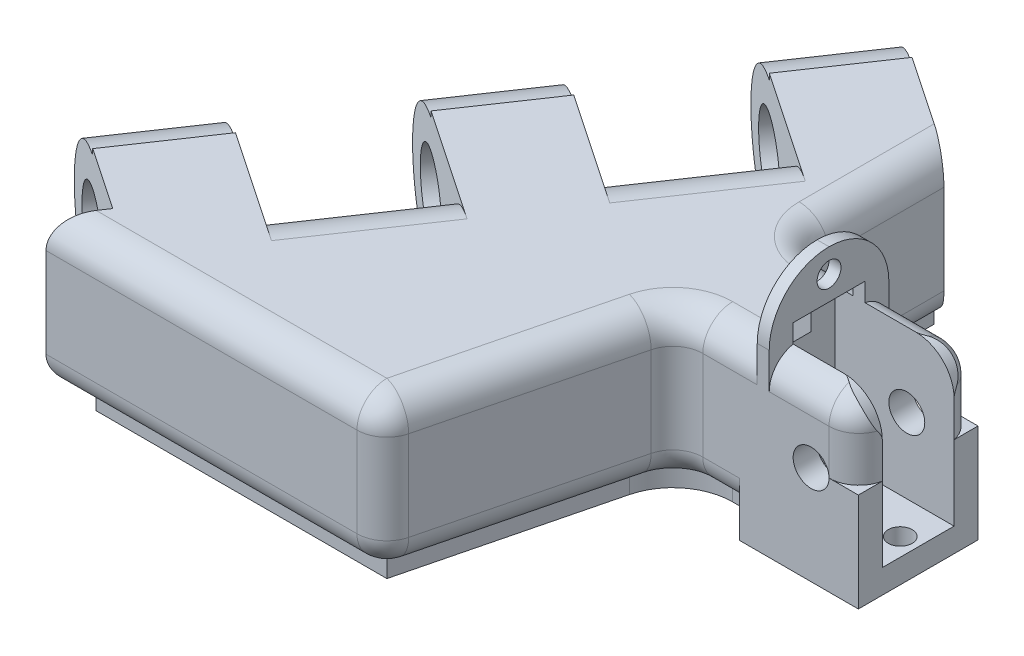
SolidWorks part; units mm, degrees
ref_plane "Front" through (0, 0, 0) normal (0, 0, 1) x (1, 0, 0)
ref_plane "Top" through (0, 0, 0) normal (0, 1, 0) x (1, 0, 0)
ref_plane "Right" through (0, 0, 0) normal (1, 0, 0) x (0, 0, -1)
sketch "Sketch1" plane through (0, 0, 0) normal (0, 1, 0) x (1, 0, 0)
  line L0 (-60, 60) -> (-60, 80)
  line L1 (-60, -60) -> (60, -60)
  line L2 (-60, -60) -> (-60, 60)
  line L3 (-60, 60) -> (60, 60)
  line L4 (60, -60) -> (60, 60)
  line L5 (-60, -60) -> (60, 60) construction
  line L6 (-60, 60) -> (60, -60) construction
  line L7 (-60, 80) -> (-40, 80)
  line L8 (-40, 80) -> (-40, 60)
  line L9 (-26.6667, 60) -> (-26.6667, 90)
  line L10 (-26.6667, 90) -> (-6.6667, 90)
  line L11 (-6.6667, 90) -> (-6.6667, 60)
  line L12 (-6.6667, 60) -> (6.6667, 60)
  line L13 (6.6667, 60) -> (6.6667, 90)
  line L14 (6.6667, 90) -> (26.6667, 90)
  line L15 (26.6667, 90) -> (26.6667, 60)
  line L16 (40, 60) -> (40, 80)
  line L17 (40, 80) -> (60, 80)
  line L18 (60, 80) -> (60, 60)
  line L19 (60, 0) -> (90, 0)
  line L20 (90, 0) -> (90, -20)
  line L21 (90, -20) -> (60, -20)
  point P0 (0, 0)
  dimension "D1" = 120
  dimension "D2" = 90
  dimension "D3" = 20
  dimension "D4" = 20
  dimension "D5" = 20
  dimension "D6" = 20
  dimension "D7" = 13.3333
  dimension "D8" = 13.3333
  dimension "D9" = 120
  dimension "D10" = 20
  dimension "D11" = 30
  dimension "D12" = 30
  dimension "D13" = 20
  dimension "D14" = 90
  dimension "D15" = 30
  dimension "D16" = 40
  dimension "D17" = 20
extrude "Boss-Extrude1" add sketch "Sketch1" along normal blind 25 contours L1 L4 L3 L2 | L18 L17 L16 L3 | L14 L13 L3 | L11 L10 L9 L3 | L8 L7 L0 L3 | L20 L19 L4 region at (0, 0, 0) region at (-50, 0, -70) region at (-16.6667, 0, -75) region at (75, 0, 10) region at (16.6667, 0, -75) region at (50, 0, -70)
sketch "Sketch3" plane through (0, 25, 0) normal (0, 1, 0) x (1, 0, 0)
  line L0 (-60, 5) -> (-30, -60)
  line L1 (-60, -60) -> (-60, 80) construction
  line L2 (-60, -60) -> (60, -60) construction
  line L3 (-30, -60) -> (-60, -60)
  line L4 (-60, -60) -> (-60, 5)
  line L5 (50, -60) -> (60, -20)
  line L6 (-60, -60) -> (60, -60) construction
  line L7 (60, -60) -> (60, -20) construction
  line L8 (60, -20) -> (60, -60)
  line L9 (60, -60) -> (50, -60)
  dimension "D1" = 40
  dimension "D2" = 10
  dimension "D3" = 30
  dimension "D4" = 65
extrude "Cut-Extrude2" cut sketch "Sketch3" against normal blind 50
sketch "Sketch5" plane through (0, 25, 0) normal (0, 1, 0) x (1, 0, 0)
fillet "Fillet3" radius 5 51 edges at (0, 25, -60) (0, 0, -60) (33.3333, 25, -60) (-33.3333, 25, -60) (-33.3333, 0, -60) (33.3333, 0, -60) (75, 25, 0) (75, 0, 0) (75, 0, 20) (75, 25, 20) (-40, 12.5, -60) (-40, 25, -70) (-40, 12.5, -80) (-40, 0, -70) (-26.6667, 12.5, -90) (-26.6667, 25, -75) (-26.6667, 12.5, -60) (-26.6667, 0, -75) (-6.6667, 12.5, -60) (-6.6667, 25, -75) (-6.6667, 12.5, -90) (-6.6667, 0, -75) (6.6667, 12.5, -90) (6.6667, 25, -75) (6.6667, 12.5, -60) (6.6667, 0, -75) (26.6667, 12.5, -60) (26.6667, 25, -75) (26.6667, 12.5, -90) (26.6667, 0, -75) (40, 12.5, -80) (40, 25, -70) (40, 12.5, -60) (40, 0, -70) (60, 12.5, 0) (60, 25, -40) (60, 12.5, -80) (60, 0, -40) (55, 0, 40) (55, 25, 40) (60, 12.5, 20) (50, 12.5, 60) (10, 0, 60) (10, 25, 60) (-45, 0, 27.5) (-45, 25, 27.5) (-30, 12.5, 60) (-60, 0, -42.5) (-60, 12.5, -80) (-60, 25, -42.5) (-60, 12.5, -5)
fillet "Fillet4" radius 5 32 edges at (41.4645, 1.4645, -78.5355) (58.5355, 1.4645, -78.5355) (8.1311, 1.4645, -88.5355) (25.2022, 1.4645, -88.5355) (-25.2022, 1.4645, -88.5355) (-8.1311, 1.4645, -88.5355) (-58.5355, 1.4645, -78.5355) (-41.4645, 1.4645, -78.5355) (-25.2022, 23.5355, -88.5355) (-8.1311, 23.5355, -88.5355) (8.1311, 23.5355, -88.5355) (25.2022, 23.5355, -88.5355) (41.4645, 23.5355, -78.5355) (58.5355, 23.5355, -78.5355) (90, 23.5355, 1.4645) (90, 12.5, 0) (90, 1.4645, 1.4645) (90, 1.4645, 18.5355) (90, 12.5, 20) (90, 23.5355, 18.5355) (-58.5355, 23.5355, -78.5355) (-41.4645, 23.5355, -78.5355) (90, 0, 10) (50, 0, -80) (16.6667, 0, -90) (-16.6667, 0, -90) (-50, 0, -80) (-16.6667, 25, -90) (16.6667, 25, -90) (50, 25, -80) (90, 25, 10) (-50, 25, -80)
sketch "Sketch6" plane through (0, 25, 0) normal (0, 1, 0) x (1, 0, 0)
  line L0 (-2.5008, -55) -> (55, 30) construction
  line L1 (-26.8008, -55) -> (46.0961, -55) construction
  line L2 (55, 5) -> (55, 75) construction
  line L3 (55, 5) -> (55, 55) construction
  line L5 (126.972, 136.3919) -> (-26.8008, -90.9212)
  line L9 (-26.8008, -90.9212) -> (-300.5369, -90.9212)
  line L10 (-300.5369, -90.9212) -> (-300.5369, 228.057)
  line L11 (-300.5369, 228.057) -> (126.972, 228.057)
  line L12 (126.972, 228.057) -> (126.972, 136.3919)
  point P10 (55, 30)
  dimension "D1" = 24.3
  dimension "D2" = 427.5089
  dimension "D3" = 318.9783
  dimension "D4" = 90
  dimension "D5" = 273.736
extrude "Cut-Extrude4" cut sketch "Sketch6" against normal through all
sketch "Sketch7" plane through (23.8097, 0, 16.1068) normal (-0.8283, 0, -0.5603) x (-0.5603, 0, 0.8283)
  line L0 (46.9566, 25) -> (-55.6657, 25) construction
  line L1 (44.9566, 0) -> (27.7766, 0)
  line L2 (44.9566, 0) -> (44.9566, 25)
  line L3 (44.9566, 25) -> (27.7766, 25)
  line L4 (27.7766, 0) -> (27.7766, 25)
  line L5 (46.9566, 0) -> (-55.6657, 0) construction
  line L6 (4.2355, 0) -> (-12.9445, 0)
  line L7 (4.2355, 0) -> (4.2355, 25)
  line L8 (4.2355, 25) -> (-12.9445, 25)
  line L9 (-12.9445, 0) -> (-12.9445, 25)
  line L10 (27.7766, 0) -> (-36.4857, 0) construction
  line L11 (-53.6657, 0) -> (-36.4857, 0)
  line L12 (-53.6657, 0) -> (-53.6657, 25)
  line L13 (-53.6657, 25) -> (-36.4857, 25)
  line L14 (-36.4857, 0) -> (-36.4857, 25)
  point P18 (-4.3545, 0)
  dimension "D1" = 17.18
  dimension "D2" = 2
  dimension "D3" = 17.18
  dimension "D4" = 17.18
  dimension "D5" = 2
extrude "Boss-Extrude2" add sketch "Sketch7" along normal blind 25
fillet "Fillet5" radius 10 4 edges at (37.6579, 0, -4.3643) (37.6579, 25, -4.3643) (14.8412, 0, 29.3643) (14.8412, 25, 29.3643)
sketch "Sketch8" plane through (-25.1899, 0, 37.2367) normal (-0.5603, 0, 0.8283) x (0.8283, 0, 0.5603)
  line L0 (3.7459, 0) -> (28.7459, 0) construction
  line L1 (3.7459, 25) -> (28.7459, 25) construction
  line L2 (16.2459, 0) -> (3.7459, 0)
  line L3 (3.7459, 0) -> (3.7459, 25)
  line L4 (3.7459, 25) -> (16.2459, 25)
  arc A0 (16.2459, 0) -> (16.2459, 25) centre (16.2459, 12.5) cw
  line M2 (28.7459, 25) -> (3.7459, 25)
  line M3 (3.7459, 25) -> (3.7459, 0)
  line M4 (3.7459, 0) -> (28.7459, 0)
extrude "Cut-Extrude5" cut sketch "Sketch8" against normal through all contours A0 L3 M4 | A0 M3 M2 region at (-19.7746, 22.2079, 40.9) region at (-19.7746, 2.7921, 40.9)
sketch "Sketch9" plane through (-25.1899, 0, 37.2367) normal (-0.5603, 0, 0.8283) x (0.8283, 0, 0.5603)
  circle A0 centre (16.2459, 12.5) radius 6.665
  arc A2 (16.2459, 25) -> (16.2459, 0) centre (16.2459, 12.5) ccw construction
  point P5 (3.7459, 12.5)
  dimension "D1" = 13.33
extrude "Cut-Extrude6" cut sketch "Sketch9" against normal through all
sketch "Sketch10" plane through (-25.1899, 0, 37.2367) normal (-0.5603, 0, 0.8283) x (0.8283, 0, 0.5603)
  line L0 (16.2459, 25) -> (16.2459, 24)
  line L1 (16.2459, 25) -> (-13.7541, 25)
  line L2 (-13.7541, 25) -> (-13.7541, 0)
  line L3 (-13.7541, 0) -> (16.2459, 0)
  line L4 (16.2459, 0) -> (16.2459, 1)
  arc A0 (16.2459, 1) -> (16.2459, 24) centre (16.2459, 12.5) cw
  dimension "D1" = 90
  dimension "D2" = 90
  dimension "D3" = 90
  dimension "D4" = 30
  dimension "D5" = 1
extrude "Cut-Extrude7" cut sketch "Sketch10" against normal through all
sketch "Sketch11" plane through (23.8097, 0, 16.1068) normal (-0.8283, 0, -0.5603) x (-0.5603, 0, 0.8283)
  line L1 (-53.6657, 0) -> (-73.6657, 0)
  line L2 (-53.6657, 0) -> (-53.6657, 25)
  line L3 (-53.6657, 25) -> (-73.6657, 25)
  line L4 (-73.6657, 0) -> (-73.6657, 25)
  dimension "D1" = 20
extrude "Cut-Extrude8" cut sketch "Sketch11" against normal blind 15
sketch "Sketch12" plane through (0, 25, 0) normal (0, 1, 0) x (1, 0, 0)
  line L1 (70, -4) -> (110, -4)
  line L2 (70, -4) -> (70, -16)
  line L3 (70, -16) -> (110, -16)
  line L4 (110, -4) -> (110, -16)
  line L5 (90, -5) -> (90, -15) construction
  line L6 (63.9039, -15) -> (85, -15) construction
  dimension "D1" = 20
  dimension "D2" = 12
  dimension "D3" = 40
  dimension "D4" = 1
extrude "Cut-Extrude9" cut sketch "Sketch12" against normal through all
sketch "Sketch13" plane through (0, 0, 20) normal (0, 0, 1) x (1, 0, 0)
  line L0 (85, 5) -> (85, 20) construction
  line L1 (82, 20) -> (82, 5) construction
  line L2 (85, 20) -> (63.9039, 20) construction
  line L3 (63.9039, 5) -> (85, 5) construction
  circle A0 centre (82, 12.5) radius 3
  dimension "D1" = 6
extrude "Cut-Extrude10" cut sketch "Sketch13" against normal through all
sketch "Sketch14" plane through (0, 0, 4) normal (0, 0, 1) x (1, 0, 0)
  line L0 (85, 24.899) -> (70, 24.899) construction
  line L1 (70, 0.101) -> (85, 0.101) construction
  line L2 (89.899, 5) -> (89.899, 20) construction
  line L3 (77.5, 24.899) -> (89.899, 24.899)
  line L4 (89.899, 24.899) -> (89.899, 0.101)
  line L5 (89.899, 0.101) -> (77.5, 0.101)
  arc A0 (77.5, 24.899) -> (77.5, 0.101) centre (77.5, 12.5) cw
  line M6 (70, 0.101) -> (85, 0.101)
  arc M7 (85, 0.101) -> (89.899, 5) centre (85, 5) ccw
  line M8 (89.899, 5) -> (89.899, 20)
  arc M9 (89.899, 20) -> (85, 24.899) centre (85, 20) ccw
  line M10 (85, 24.899) -> (70, 24.899)
extrude "Cut-Extrude11" [suppressed] cut sketch "Sketch14" against normal through all both and the other way through all contours L4 L3 M9 | A0 L4 M10 M9 | A0 M8 M6 M7 | L5 L4 M7
sketch "Sketch16" plane through (0, 0, 20) normal (0, 0, 1) x (1, 0, 0)
  line L0 (85, 12.5) -> (89.899, 12.5)
  line L1 (89.899, 20) -> (89.899, 5) construction
  line L2 (70, 12.5) -> (70, 0.101)
  line L3 (79, 12.5) -> (70, 12.5)
  line L4 (85, 0.101) -> (70, 0.101) construction
  line L5 (70, 0.101) -> (85, 0.101)
  line L6 (89.899, 12.5) -> (89.899, 5)
  line L7 (70, 0.101) -> (70, 24.899) construction
  circle A0 centre (82, 12.5) radius 3 construction
  arc A1 (85, 0.101) -> (89.899, 5) centre (85, 5) ccw
  arc A2 (79, 12.5) -> (85, 12.5) centre (82, 12.5) ccw
  dimension "D1" = 3
extrude "Boss-Extrude3" add sketch "Sketch16" against normal up to surface (20 mm away) up to face at (77.3333, 12.5, 0)
sketch "Sketch17" plane through (0, 12.5, 0) normal (0, 1, 0) x (1, 0, 0)
  line L1 (89.899, -16) -> (70, -16)
  line L2 (89.899, -16) -> (89.899, -4)
  line L3 (89.899, -4) -> (70, -4)
  line L4 (70, -16) -> (70, -4)
extrude "Cut-Extrude12" cut sketch "Sketch17" against normal through all
sketch "Sketch18" plane through (0, 0, 0) normal (0, -1, 0) x (-1, 0, 0)
  line L4 (-89.899, 0) -> (-89.899, -20)
  line L7 (-89.899, 0) -> (-89.899, -4) construction
  line L8 (-89.899, 0) -> (-70, 0)
  line L9 (-70, 0) -> (-70, -5)
  line L10 (-55, 5) -> (-55, 27.5854)
  line L11 (-55, 27.5854) -> (-43.5259, 35.3474)
  line L12 (-43.5259, 35.3474) -> (-33.8997, 21.1175)
  line L13 (-33.8997, 21.1175) -> (-52.536, 8.5104)
  line L14 (-52.536, 8.5104) -> (-39.3455, -10.9882)
  line L15 (-39.3455, -10.9882) -> (-20.7092, 1.6189)
  line L16 (-20.7092, 1.6189) -> (-11.083, -12.611)
  line L17 (-11.083, -12.611) -> (-29.7193, -25.2181)
  line L18 (-29.7193, -25.2181) -> (-16.5288, -44.7167)
  line L19 (-16.5288, -44.7167) -> (2.1075, -32.1097)
  line L20 (2.1075, -32.1097) -> (11.7337, -46.3395)
  line L21 (11.7337, -46.3395) -> (1.3802, -53.3434)
  line L22 (1.3802, -53.3434) -> (2.5008, -55)
  line L23 (2.5008, -55) -> (-46.0961, -55)
  line L24 (-46.0961, -55) -> (-54.2025, -22.5746)
  line L25 (-70, -5) -> (-65, -5)
  line L26 (-89.899, -20) -> (-70, -20)
  line L27 (-70, -20) -> (-70, -15)
  line L28 (-70, -15) -> (-63.9039, -15)
  line L29 (-70, -16) -> (-70, -20) construction
  line L30 (-70, -20) -> (-85, -20) construction
  line L31 (-70, 0) -> (-70, -4) construction
  line L32 (-11.083, -12.611) -> (-29.7193, -25.2181) construction
  arc A0 (-65, -5) -> (-55, 5) centre (-65, 5) ccw
  arc A1 (-63.9039, -15) -> (-54.2025, -22.5746) centre (-63.9039, -25) cw
extrude "Boss-Extrude4" add sketch "Sketch18" along normal blind 4
sketch "Sketch19" plane through (0, 12.5, 0) normal (0, 1, 0) x (1, 0, 0)
  line L1 (89.899, -4) -> (85, -4)
  line L2 (89.899, -4) -> (89.899, 0)
  line L3 (89.899, 0) -> (85, 0)
  line L4 (85, -4) -> (85, 0)
  line L5 (89.899, -16) -> (85, -16)
  line L6 (89.899, -16) -> (89.899, -20)
  line L7 (89.899, -20) -> (85, -20)
  line L8 (85, -16) -> (85, -20)
extrude "Boss-Extrude5" add sketch "Sketch19" against normal up to surface (16.5 mm away) up to face at (42.7188, -4, 14.1301)
sketch "Sketch20" plane through (0, 0, 20) normal (0, 0, 1) x (1, 0, 0)
  line L1 (85, 0) -> (70, 0)
  line L2 (85, 0) -> (85, 0.101)
  line L3 (85, 0.101) -> (70, 0.101)
  line L4 (70, 0) -> (70, 0.101)
extrude "Boss-Extrude6" add sketch "Sketch20" against normal up to surface (4 mm away) up to face at (83.2139, 10.4393, 16)
sketch "Sketch21" plane through (0, 0, 0) normal (0, 0, -1) x (-1, 0, 0)
  line L1 (-70, 0) -> (-85, 0)
  line L2 (-70, 0) -> (-70, 0.101)
  line L3 (-70, 0.101) -> (-85, 0.101)
  line L4 (-85, 0) -> (-85, 0.101)
extrude "Boss-Extrude7" add sketch "Sketch21" against normal up to surface (4 mm away) up to face at (79, 12.5, 4)
sketch "Sketch23" plane through (0, 0, 20) normal (0, 0, 1) x (1, 0, 0)
  line L0 (70, 24.899) -> (85, 24.899) construction
  line L1 (89.899, 20) -> (89.899, 12.5) construction
  line L2 (83.5, 24.899) -> (89.899, 24.899)
  line L3 (89.899, 24.899) -> (89.899, 18.5)
  arc A0 (83.5, 24.899) -> (89.899, 18.5) centre (83.5, 18.5) cw
  dimension "D1" = 1.5
  dimension "D2" = 1.5
extrude "Cut-Extrude13" cut sketch "Sketch23" against normal through all
sketch "Sketch24" plane through (0, -4, 0) normal (0, -1, 0) x (-1, 0, 0)
  line L0 (-89.899, 0) -> (-89.899, -20) construction
  circle A0 centre (-86.899, -10) radius 2
  point P4 (-89.899, -10)
  dimension "D1" = 4
  dimension "D2" = 3
extrude "Cut-Extrude14" cut sketch "Sketch24" against normal through all
sketch "Sketch25" plane through (0, -4, 0) normal (0, -1, 0) x (-1, 0, 0)
  line L0 (-89.899, 0) -> (-89.899, -20) construction
  line L1 (-52.899, -12) -> (-56.899, -12)
  line L2 (-52.899, -12) -> (-52.899, -8)
  line L3 (-52.899, -8) -> (-56.899, -8)
  line L4 (-56.899, -12) -> (-56.899, -8)
  point P6 (-56.899, -10)
  point P7 (-89.899, -10)
  dimension "D1" = 33
  dimension "D2" = 4
  dimension "D3" = 4
extrude "Boss-Extrude8" add sketch "Sketch25" along normal blind 2
sketch "Sketch26" plane through (0, 0, 12) normal (0, 0, 1) x (1, 0, 0)
  line L0 (52.899, -4) -> (56.899, -6)
  line L1 (56.899, -6) -> (56.899, -4) construction
  line L3 (56.899, -6) -> (52.899, -6)
  line L4 (52.899, -6) -> (52.899, -4)
extrude "Cut-Extrude15" cut sketch "Sketch26" against normal through all
sketch "Sketch27" plane through (8.9798, 17.9596, 0) normal (-0.4472, -0.8944, 0) x (-0.8944, 0.4472, 0)
  line L1 (-49.1031, -12) -> (-53.5753, -12)
  line L2 (-49.1031, -12) -> (-49.1031, -8)
  line L3 (-49.1031, -8) -> (-53.5753, -8)
  line L4 (-53.5753, -12) -> (-53.5753, -8)
extrude "Cut-Extrude16" cut sketch "Sketch27" against normal through all
sketch "Sketch28" plane through (0, -4, 0) normal (0, -1, 0) x (-1, 0, 0)
  line L0 (-70, 0) -> (-89.899, 0) construction
  line L1 (-73, 0) -> (-75, 0)
  line L2 (-73, 0) -> (-73, -4)
  line L3 (-73, -4) -> (-75, -4)
  line L4 (-75, 0) -> (-75, -4)
  line L5 (-89.899, -20) -> (-70, -20) construction
  line L6 (-73, -20) -> (-75, -20)
  line L7 (-73, -20) -> (-73, -16)
  line L8 (-73, -16) -> (-75, -16)
  line L9 (-75, -20) -> (-75, -16)
  line L10 (-70, -4) -> (-89.899, -4) construction
  line L12 (-89.899, -16) -> (-70, -16) construction
  dimension "D1" = 2
  dimension "D2" = 3
  dimension "D3" = 2
extrude "Boss-Extrude9" add sketch "Sketch28" against normal blind 40
sketch "Sketch29" plane through (0, 0, 20) normal (0, 0, 1) x (1, 0, 0)
  line L0 (75, 36) -> (75, 20) construction
  line L1 (73, 36) -> (75, 36)
  line L2 (73, 36) -> (73, 28)
  line L3 (73, 28) -> (75, 28)
  line L4 (75, 36) -> (75, 28)
  dimension "D1" = 8
extrude "Boss-Extrude10" add sketch "Sketch29" against normal up to surface (20 mm away) up to face at (76.5229, 14.7308, 0)
fillet "Fillet6" radius 10 2 edges at (74, 36, 20) (74, 36, 0)
sketch "Sketch30" plane through (75, 0, 0) normal (1, 0, 0) x (0, 0, -1)
  line L0 (-10, 28) -> (-10, 36) construction
  line L1 (-4, 28) -> (-16, 28) construction
  circle A0 centre (-10, 32) radius 2
  dimension "D1" = 4
extrude "Cut-Extrude17" cut sketch "Sketch30" against normal through all
scale "Scale2" scale about centroid uniform scaling yes scale factor 0.75
